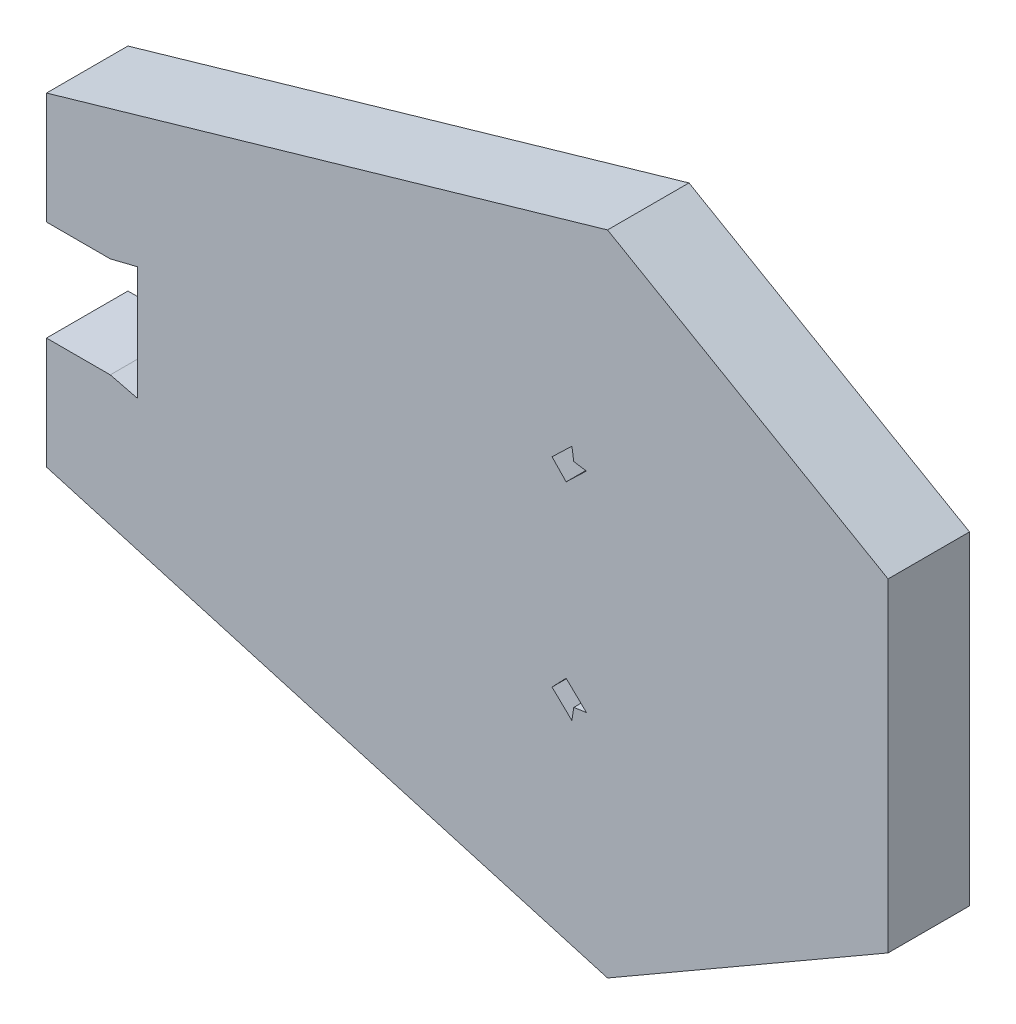
SolidWorks part; units mm, degrees
ref_plane "Front Plane" through (0, 0, 0) normal (0, 0, 1) x (1, 0, 0)
ref_plane "Top Plane" through (0, 0, 0) normal (0, 1, 0) x (1, 0, 0)
ref_plane "Right Plane" through (0, 0, 0) normal (1, 0, 0) x (0, 0, -1)
sketch "Sketch1" plane through (0, 0, 0) normal (0, 0, 1) x (1, 0, 0)
  line L0 (25.85, 11.9319) -> (5.1833, 23.8638) construction
  line L1 (25.85, -11.9319) -> (25.85, 11.9319) construction
  line L2 (5.1833, -23.8638) -> (25.85, -11.9319) construction
  line L3 (5.1833, -23.8638) -> (-36.15, -11.9319) construction
  line L4 (-36.15, 11.9319) -> (-36.15, -11.9319) construction
  line L5 (-36.15, 11.9319) -> (5.1833, 23.8638) construction
  line L6 (25.85, 11.9319) -> (5.1833, 23.8638)
  line L7 (25.85, -11.9319) -> (25.85, 11.9319)
  line L8 (5.1833, -23.8638) -> (25.85, -11.9319)
  line L9 (5.1833, -23.8638) -> (-36.15, -11.9319)
  line L10 (-36.15, 11.9319) -> (-36.15, -11.9319)
  line L11 (-36.15, 11.9319) -> (5.1833, 23.8638)
  line L18 (-36.15, 3.7) -> (-31.45, 3.7)
  line L19 (-31.45, 3.7) -> (-29.45, 4.1966)
  line L20 (-17.4796, 7.1692) -> (-31.45, 3.7) construction
  line L21 (-29.45, 4.1966) -> (-29.45, -4.1966)
  line L23 (-17.4796, -7.1692) -> (-31.45, -3.7) construction
  line L24 (-29.45, -4.1966) -> (-31.45, -3.7)
  line L25 (-31.45, -3.7) -> (-36.15, -3.7)
  line L26 (-34.55, 3.7) -> (-32.95, 3.7) construction
  line L27 (-31.45, 3.7) -> (-31.45, 1.5) construction
  line L28 (-36.15, 0) -> (25.85, 0) construction
  line L29 (2.5578, -8.7529) -> (1.0937, -7.3455)
  line L30 (1.0937, -7.3455) -> (2.1327, -6.2646)
  line L31 (2.1327, -6.2646) -> (3.6298, -7.7037)
  line L32 (3.6298, -7.7037) -> (2.6946, -7.8446)
  line L33 (2.6946, 7.8446) -> (2.5578, 8.7529)
  line L34 (2.6946, 7.8446) -> (2.5578, 8.7529)
  line L35 (3.6298, 7.7037) -> (2.6946, 7.8446)
  line L36 (3.6298, 7.7037) -> (2.6946, 7.8446)
  line L37 (2.1327, 6.2646) -> (3.6298, 7.7037)
  line L38 (2.1327, 6.2646) -> (3.6298, 7.7037)
  line L39 (1.0937, 7.3455) -> (2.1327, 6.2646)
  line L40 (1.0937, 7.3455) -> (2.1327, 6.2646)
  line L41 (2.5578, 8.7529) -> (1.0937, 7.3455)
  line L42 (2.5578, 8.7529) -> (1.0937, 7.3455)
  line L43 (2.6946, -7.8446) -> (2.5578, -8.7529)
  dimension "D1" = 2
  dimension "D2" = 0
extrude "Boss-Extrude1" add sketch "Sketch1" along normal blind 6 contours L28 L21 L24 L25 L10 L9 L8 L7 | L21 L28 L7 L6 L11 L10 L18 L19 region at (-3.3453, 9.4577, 0) region at (-3.3453, -9.4577, 0)
